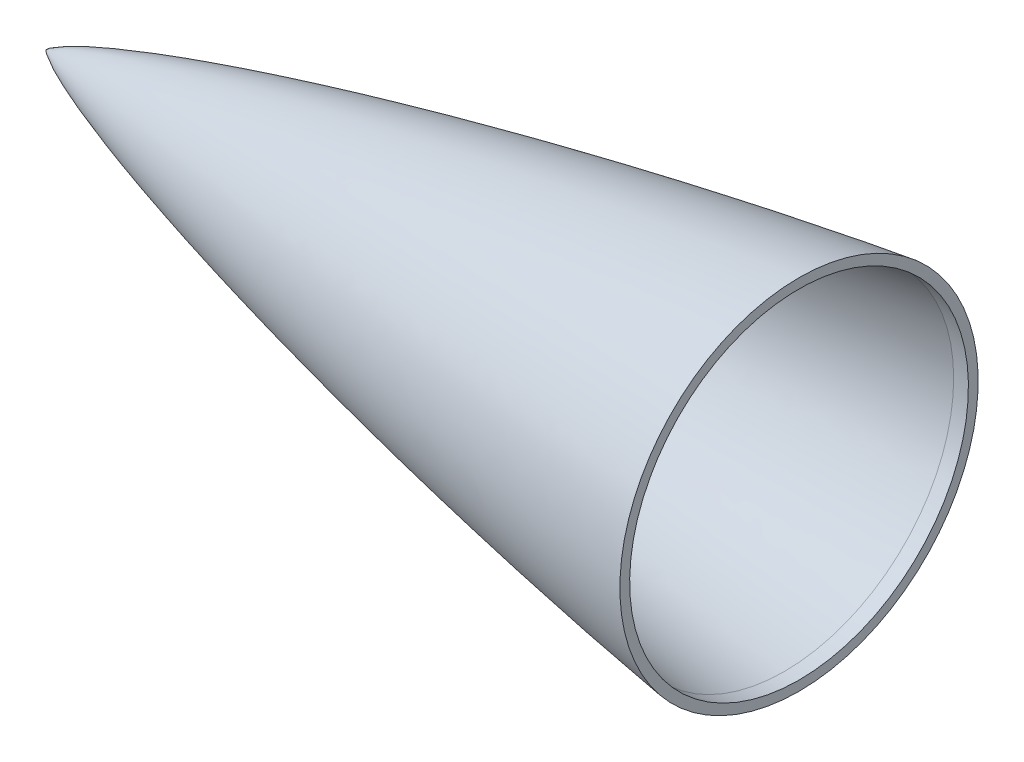
SolidWorks part; units mm, degrees
material "ABS"
ref_plane "Front Plane" through (0, 0, 0) normal (0, 0, 1) x (1, 0, 0)
ref_plane "Top Plane" through (0, 0, 0) normal (0, 1, 0) x (1, 0, 0)
ref_plane "Right Plane" through (0, 0, 0) normal (1, 0, 0) x (0, 0, -1)
sketch "Sketch1" plane through (0, 0, 0) normal (0, 0, 1) x (1, 0, 0)
  line L0 (-251.1062, 0) -> (0, 0)
  line L1 (0, 0) -> (0, 53.975)
  spline S0 degree 4 poles (-251.1062, 0) (-251.1034, 0.0111) (-251.0957, 0.0326) (-251.0721, 0.0721) (-251.0336, 0.1241) (-250.9863, 0.1789) (-250.9178, 0.2502) (-250.8219, 0.3408) (-250.6727, 0.4684) (-250.4184, 0.6641) (-249.9876, 0.9611) (-249.2261, 1.4283) (-247.8314, 2.1853) (-245.3164, 3.3841) (-241.1121, 5.1461) (-233.6085, 7.9314) (-222.9114, 11.4247) (-209.543, 15.3553) (-194.1424, 19.4912) (-178.5223, 23.3904) (-162.8469, 27.0612) (-147.1267, 30.5343) (-131.3678, 33.8274) (-115.5746, 36.9514) (-99.7499, 39.9115) (-83.8954, 42.7079) (-68.0121, 45.336) (-52.1001, 47.7849) (-36.1588, 50.0352) (-22.6625, 51.7379) (-12.3826, 52.8766) (-5.3328, 53.5502) (-2.2866, 53.8072) (-0.7626, 53.9244) (0, 53.975) knots 0 0 0 0 0 0.000177 0.000355 0.000709 0.001004 0.001299 0.001888 0.002757 0.004048 0.006275 0.010003 0.016613 0.028658 0.049486 0.080709 0.140768 0.203215 0.265661 0.328107 0.390553 0.452999 0.515445 0.577892 0.640338 0.702784 0.76523 0.827676 0.890122 0.952569 0.976284 0.988142 1 1 1 1 1 construction
  spline S1 degree 4 poles (-251.1062, 0) (-251.1034, 0.0111) (-251.0957, 0.0326) (-251.0721, 0.0721) (-251.0336, 0.1241) (-250.9863, 0.1789) (-250.9178, 0.2502) (-250.8219, 0.3408) (-250.6727, 0.4684) (-250.4184, 0.6641) (-249.9876, 0.9611) (-249.2261, 1.4283) (-247.8314, 2.1853) (-245.3164, 3.3841) (-241.1121, 5.1461) (-233.6085, 7.9314) (-222.9114, 11.4247) (-209.543, 15.3553) (-194.1424, 19.4912) (-178.5223, 23.3904) (-162.8469, 27.0612) (-147.1267, 30.5343) (-131.3678, 33.8274) (-115.5746, 36.9514) (-99.7499, 39.9115) (-83.8954, 42.7079) (-68.0121, 45.336) (-52.1001, 47.7849) (-36.1588, 50.0352) (-22.6625, 51.7379) (-12.3826, 52.8766) (-5.3328, 53.5502) (-2.2866, 53.8072) (-0.7626, 53.9244) (0, 53.975) knots 0 0 0 0 0 0.000177 0.000355 0.000709 0.001004 0.001299 0.001888 0.002757 0.004048 0.006275 0.010003 0.016613 0.028658 0.049486 0.080709 0.140768 0.203215 0.265661 0.328107 0.390553 0.452999 0.515445 0.577892 0.640338 0.702784 0.76523 0.827676 0.890122 0.952569 0.976284 0.988142 1 1 1 1 1
  dimension "D1" = 53.975
  dimension "D2" = 251.1062
revolve "Revolve1" add sketch "Sketch1" angle 360 about L0
shell "Shell1" thickness 2.032 removed face at (0, -53.975, 0)
sketch "Sketch4" plane through (0, 0, 0) normal (0, 0, 1) x (1, 0, 0)
  line L0 (0, 53.975) -> (0, 45.72)
  line L1 (0, 45.72) -> (-65.3503, 45.72)
  line L2 (-65.3503, 45.72) -> (0, 53.975)
  spline S0 degree 3 poles (0, 53.975) (-0.0829, 53.9694) (-0.2488, 53.9583) (-0.4975, 53.9409) (-0.8291, 53.917) (-1.2948, 53.8821) (-1.7861, 53.8437) (-2.2568, 53.8059) (-2.8012, 53.7614) (-3.901, 53.6689) (-5.3737, 53.5386) (-7.0739, 53.3805) (-8.6285, 53.2305) (-10.2751, 53.0665) (-12.6426, 52.8236) (-15.5468, 52.5122) (-18.8075, 52.1462) (-21.8627, 51.7908) (-24.9174, 51.4242) (-28.7441, 50.9512) (-32.9806, 50.4085) (-37.6291, 49.7909) (-42.3452, 49.145) (-47.353, 48.4373) (-52.6065, 47.6714) (-58.3493, 46.8102) (-64.6648, 45.8338) (-71.6779, 44.7136) (-78.8681, 43.5284) (-85.999, 42.3165) (-93.3479, 41.0317) (-100.8212, 39.6881) (-108.6998, 38.2299) (-116.5935, 36.7268) (-124.2192, 35.2332) (-131.5064, 33.7682) (-138.4128, 32.3456) (-145.2511, 30.9027) (-151.6966, 29.5097) (-157.7724, 28.1666) (-163.445, 26.8861) (-169.0897, 25.5847) (-174.7346, 24.2547) (-180.2783, 22.9185) (-185.1935, 21.7064) (-189.5135, 20.6197) (-193.3393, 19.6404) (-197.3301, 18.6002) (-201.2014, 17.5706) (-204.9137, 16.5627) (-208.4169, 15.5931) (-211.8606, 14.6201) (-215.1323, 13.6747) (-217.8928, 12.8601) (-220.2458, 12.1531) (-222.4922, 11.467) (-224.7329, 10.7694) (-226.9624, 10.0609) (-229.0671, 9.3781) (-231.0215, 8.7297) (-232.7712, 8.1364) (-234.2601, 7.6215) (-235.615, 7.1441) (-236.9692, 6.6578) (-238.3756, 6.1416) (-239.6547, 5.6596) (-240.7914, 5.221) (-241.7459, 4.845) (-242.7067, 4.4573) (-243.6225, 4.0785) (-244.3835, 3.755) (-245.0313, 3.4729) (-245.5628, 3.2372) (-246.119, 2.9849) (-246.6521, 2.737) (-247.1425, 2.5028) (-247.5524, 2.3017) (-247.9325, 2.1107) (-248.2976, 1.9228) (-248.685, 1.7168) (-248.9975, 1.5445) (-249.2726, 1.3883) (-249.4893, 1.2616) (-249.7218, 1.1211) (-249.9086, 1.0042) (-250.0934, 0.8842) (-250.2393, 0.7859) (-250.3722, 0.6927) (-250.4758, 0.6174) (-250.5699, 0.5465) (-250.6563, 0.4788) (-250.7365, 0.4131) (-250.808, 0.3515) (-250.8706, 0.2947) (-250.9236, 0.2436) (-250.9668, 0.1991) (-251.003, 0.1593) (-251.0352, 0.121) (-251.058, 0.0907) (-251.0725, 0.0694) (-251.0797, 0.0584) (-251.0878, 0.0451) (-251.0946, 0.0322) (-251.1, 0.0196) (-251.1035, 0.0099) (-251.1053, 0.0033) (-251.1062, 0) knots 0 0 0 0 0.000967 0.001934 0.002902 0.004836 0.007369 0.008635 0.010332 0.013724 0.021479 0.027537 0.033595 0.039653 0.046793 0.061289 0.073642 0.084975 0.097081 0.109444 0.129843 0.146782 0.164012 0.185236 0.205635 0.225792 0.252809 0.28 0.308436 0.337608 0.36417 0.39525 0.425968 0.457408 0.488756 0.516391 0.543904 0.570811 0.597718 0.62064 0.64322 0.665389 0.688048 0.710707 0.731747 0.746958 0.762544 0.777702 0.79495 0.809159 0.822464 0.837248 0.8508 0.862094 0.870741 0.879391 0.889426 0.89805 0.906612 0.915175 0.922012 0.928111 0.933507 0.93873 0.944854 0.95094 0.954636 0.959032 0.962878 0.966692 0.970564 0.9725 0.974915 0.97733 0.979607 0.981757 0.983654 0.984919 0.986708 0.988432 0.990025 0.99086 0.992112 0.992947 0.99402 0.994676 0.995511 0.996068 0.996565 0.997002 0.997439 0.997841 0.998209 0.998537 0.998825 0.999066 0.999258 0.999451 0.999648 0.999699 0.99975 0.999801 0.999881 0.99992 0.99996 1 1 1 1 construction
  dimension "D1" = 45.72
ref_axis "Axis1" through (-263.6615, 0, 0) along (1, 0, 0)
revolve "Revolve2" add sketch "Sketch4" angle 360 about axis through (-263.6615, 0, 0) along (1, 0, 0)
sketch "Sketch5" plane through (0, 0, 0) normal (1, 0, 0) x (0, 0, -1)
  circle A0 centre (0, 0) radius 45.72
  circle A1 centre (0, 0) radius 50.8
  circle A2 centre (0, 0) radius 45.72 construction
  dimension "D1" = 101.6
extrude "Boss-Extrude1" add sketch "Sketch5" along normal blind 76.2
sketch "Sketch6" plane through (0, 0, 0) normal (0, 0, 1) x (1, 0, 0)
  line L1 (153.0817, 96.1546) -> (-47.9062, 96.1546)
  line L2 (153.0817, 96.1546) -> (153.0817, -107.4473)
  line L3 (153.0817, -107.4473) -> (-47.9062, -107.4473)
  line L4 (-47.9062, 96.1546) -> (-47.9062, -107.4473)
  dimension "D1" = 203.2
extrude "Cut-Extrude1" cut sketch "Sketch6" against normal through all both and the other way through all
